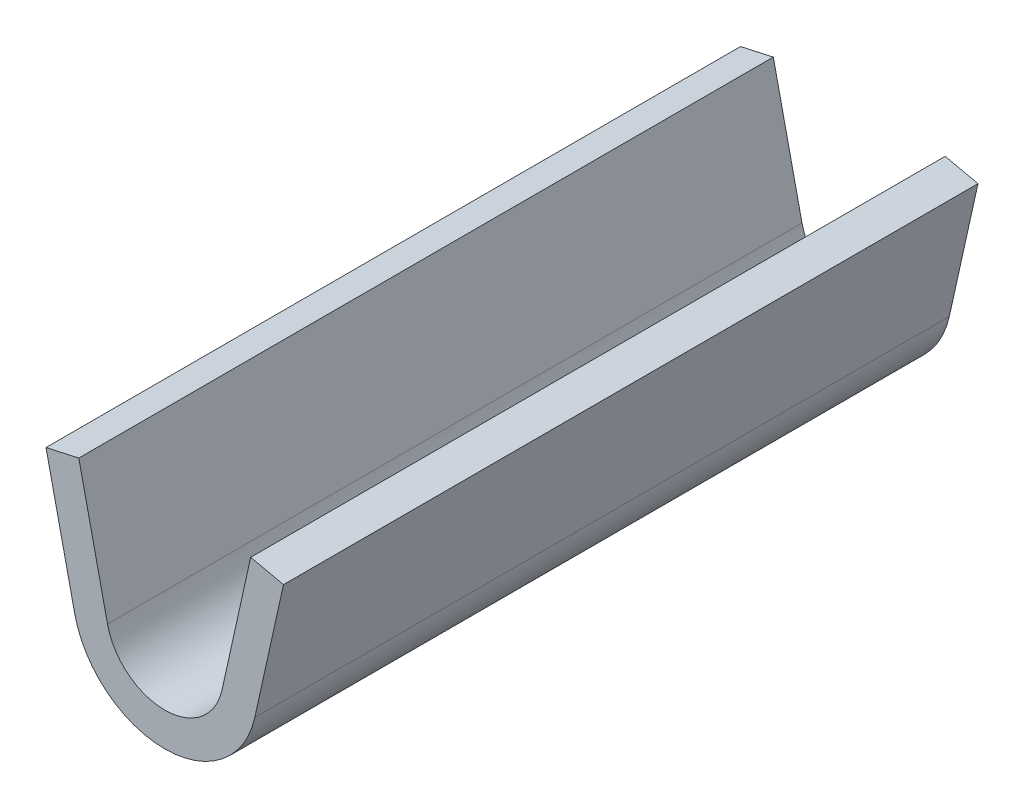
SolidWorks part; units mm, degrees
material "Copper"
ref_plane "Front" through (0, 0, 0) normal (0, 0, 1) x (1, 0, 0)
ref_plane "Top" through (0, 0, 0) normal (0, 1, 0) x (1, 0, 0)
ref_plane "Right" through (0, 0, 0) normal (1, 0, 0) x (0, 0, -1)
sketch "Sketch1" plane through (0, 0, 0) normal (0, 0, 1) x (1, 0, 0)
  line L0 (0.53, 0.4882) -> (0.402, -0.0891)
  line L1 (-0.402, -0.0891) -> (-0.53, 0.4882)
  line L2 (-0.53, 0.4882) -> (0.53, 0.4882) construction
  arc A0 (0.402, -0.0891) -> (-0.402, -0.0891) centre (0, 0) cw
  dimension "D1" = 25
  dimension "D2" = 0.9
  dimension "D3" = 1.06
extrude "Extrude-Thin1" add sketch "Sketch1" along normal blind 3.1 thin thin type one direction wall 0.15
other "CPoint1" parameters "Diameter"=0.69, "Stub Length"=0
ref_axis "Axis1" through (0, 0, -10) along (0, 0, 1)
